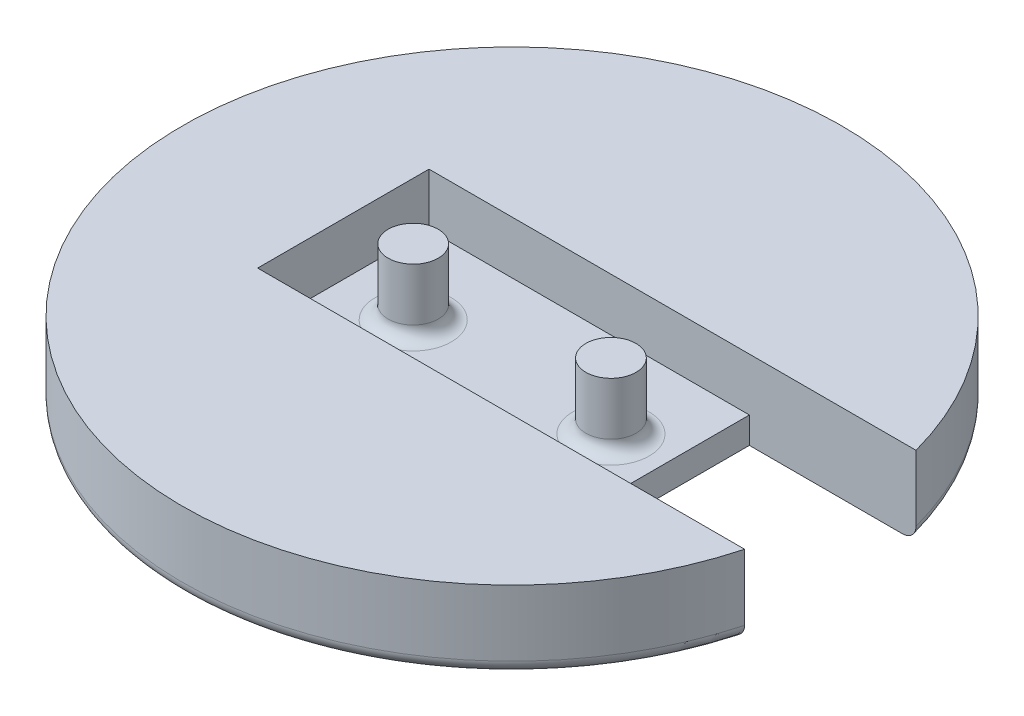
SolidWorks part; units mm, degrees
ref_plane "Front Plane" through (0, 0, 0) normal (0, 0, 1) x (1, 0, 0)
ref_plane "Top Plane" through (0, 0, 0) normal (0, 1, 0) x (1, 0, 0)
ref_plane "Right Plane" through (0, 0, 0) normal (1, 0, 0) x (0, 0, -1)
sketch "Sketch1" plane through (0, 0, 0) normal (0, 1, 0) x (1, 0, 0)
  line L0 (-25, 0) -> (25, 0) construction
  line L1 (0, 25) -> (0, -25) construction
  line L3 (-12.8, 6.5) -> (25, 6.5)
  line L4 (-12.8, 6.5) -> (-12.8, -6.5)
  line L5 (-12.8, -6.5) -> (25, -6.5)
  line L6 (25, 6.5) -> (25, -6.5)
  line L7 (6.1, -6.5) -> (6.1, 6.5) construction
  line L8 (-12.8, 0) -> (25, 0) construction
  circle A0 centre (0, 0) radius 25
  circle A1 centre (-7.5, 0) radius 1.9
  circle A2 centre (7.5, 0) radius 1.9
  point P11 (6.1, 0)
  dimension "D1" = 50
  dimension "D3" = 3.8
  dimension "D2" = 7.5
  dimension "D4" = 13
  dimension "D5" = 5.3
extrude "Boss-Extrude1" add sketch "Sketch1" along normal blind 2 contours L3 A0 L5 L4 | L5 A0 L3 L4 A1 A2 | A1 | A2 region at (-13.5011, 0, 0) region at (5.6701, 0, -6.1003) region at (-7.5, 0, 0) region at (7.5, 0, 0)
sketch "Sketch2" plane through (0, 2, 0) normal (0, 1, 0) x (1, 0, 0)
  line L0 (-12.8, -6.5) -> (25, -6.5) construction
  line L1 (-12.8, 6.5) -> (-12.8, -6.5) construction
  line L2 (-12.8, 6.5) -> (25, 6.5) construction
  line L3 (-12.8, -6.5) -> (25, -6.5)
  line L4 (-12.8, 6.5) -> (-12.8, -6.5)
  line L5 (-12.8, 6.5) -> (25, 6.5)
  circle A1 centre (0, 0) radius 25
  circle A2 centre (0, 0) radius 25
  circle M2 centre (0, 0) radius 25
  dimension "D1" = 0
extrude "Boss-Extrude2" add sketch "Sketch2" along normal blind 4 contours L4 L5 L3 M2 region at (5.6701, 2, 7.2011)
sketch "Sketch3" plane through (0, 2, 0) normal (0, 1, 0) x (1, 0, 0)
  line L0 (-12.8, 6.5) -> (25, 6.5) construction
  line L1 (11.5, 6.5) -> (25, 6.5)
  line L2 (11.5, 6.5) -> (11.5, -6.5)
  line L3 (11.5, -6.5) -> (25, -6.5)
  line L4 (25, 6.5) -> (25, -6.5)
  dimension "D1" = 4
extrude "Cut-Extrude1" cut sketch "Sketch3" against normal up to next
sketch "Sketch4" plane through (0, 2, 0) normal (0, 1, 0) x (1, 0, 0)
  circle A0 centre (7.5, 0) radius 1.9 construction
  circle A1 centre (-7.5, 0) radius 1.9 construction
  circle A2 centre (7.5, 0) radius 1.9
  circle A3 centre (-7.5, 0) radius 1.9
extrude "Boss-Extrude3" add sketch "Sketch4" along normal blind 5
fillet "Fillet1" radius 1 2 edges at (7.5, 2, 1.9) (-7.5, 2, 1.9)
fillet "Fillet2" radius 1 1 edges at (-25, 0, 0)
